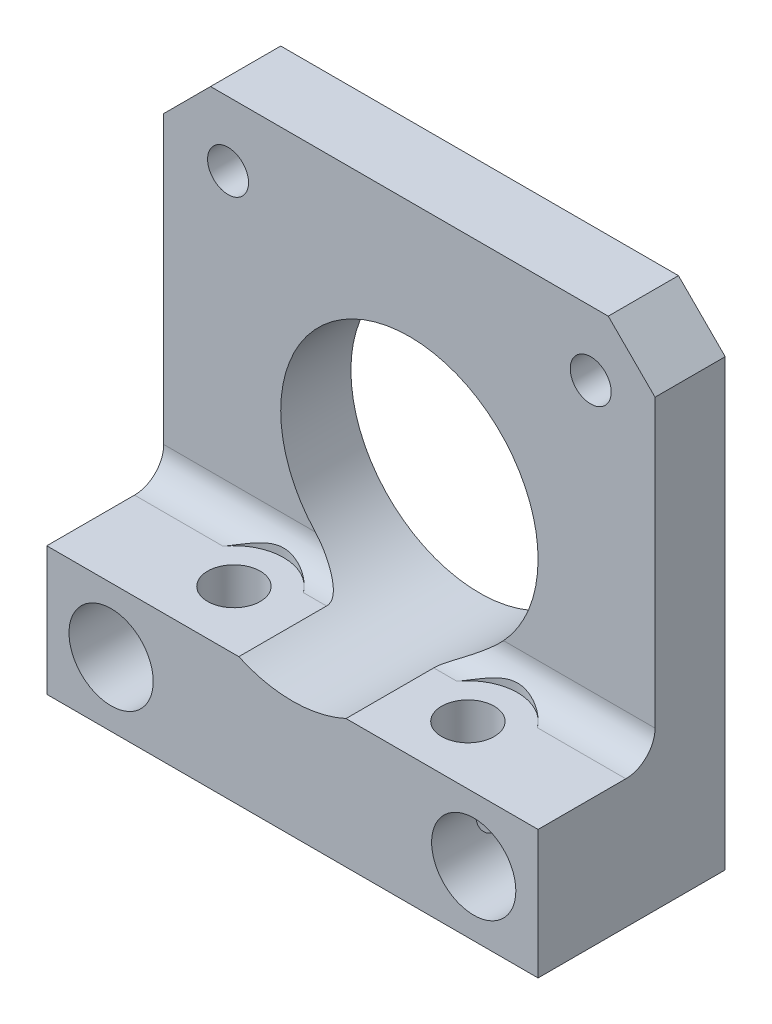
SolidWorks part; units mm, degrees
ref_plane "Plano frontal" through (0, 0, 0) normal (0, 0, 1) x (1, 0, 0)
ref_plane "Plano superior" through (0, 0, 0) normal (0, 1, 0) x (1, 0, 0)
ref_plane "Plano direito" through (0, 0, 0) normal (1, 0, 0) x (0, 0, -1)
sketch "Esboço1" plane through (0, 0, 0) normal (0, 0, 1) x (1, 0, 0)
  line L5 (21, 21) -> (-21, 21)
  line L6 (21, 21) -> (21, -21)
  line L7 (21, -21) -> (-21, -21)
  line L12 (-21, 21) -> (-21, -21)
  line L13 (21, 21) -> (-21, -21) construction
  line L14 (21, -21) -> (-21, 21) construction
  point P0 (0, 0)
  point P1 (0, 0)
  dimension "D1" = 42
  dimension "D2" = 42
extrude "Ressalto-extrusão3" add sketch "Esboço1" along normal blind 6
sketch "Esboço7" plane through (0, 0, 6) normal (0, 0, 1) x (1, 0, 0)
  line L0 (21, -21) -> (21, 21) construction
  line L1 (-21, -21) -> (21, -21)
  line L2 (-21, -21) -> (-21, -10)
  line L3 (-21, -10) -> (21, -10)
  line L4 (21, -21) -> (21, -10)
  dimension "D1" = 11
extrude "Ressalto-extrusão4" add sketch "Esboço7" along normal blind 10
sketch "Esboço6" plane through (0, 0, 0) normal (0, 0, -1) x (-1, 0, 0)
  line L0 (0, 21) -> (0, -21) construction
  line L1 (-21, 21) -> (21, 21) construction
  line L2 (21, -21) -> (-21, -21) construction
  line L4 (-15.5, 15.5) -> (15.5, 15.5) construction
  line L5 (-15.5, 15.5) -> (-15.5, -15.5) construction
  line L6 (-15.5, -15.5) -> (15.5, -15.5) construction
  line L7 (15.5, 15.5) -> (15.5, -15.5) construction
  line L8 (-15.5, 15.5) -> (15.5, -15.5) construction
  line L9 (-15.5, -15.5) -> (15.5, 15.5) construction
  circle A0 centre (0, 0) radius 11
  circle A1 centre (-15.5, 15.5) radius 1.75
  circle A2 centre (15.5, 15.5) radius 1.75
  circle A3 centre (15.5, -15.5) radius 1.75
  circle A4 centre (-15.5, -15.5) radius 1.75
  dimension "D1" = 22
  dimension "D3" = 3.5
  dimension "D2" = 31
extrude "Corte-extrusão3" cut sketch "Esboço6" against normal up to surface (16 mm away) up to face at (0, -15.5, 16)
chamfer "Chanfro1" distance 4 angle 45 2 edges at (-21, 21, 3) (21, 21, 3)
fillet "Filete1" radius 2.5 2 edges at (-12.7913, -10, 6) (12.7913, -10, 6)
sketch "Esboço8" plane through (0, -21, 0) normal (0, -1, 0) x (1, 0, 0)
  line L0 (0, 16) -> (0, 6) construction
  line L1 (-21, 16) -> (21, 16) construction
  line L2 (-13.75, 6) -> (-17.25, 6) construction
  line L3 (-10, 11) -> (10, 11) construction
  circle A0 centre (-10, 11) radius 2.25
  circle A1 centre (10, 11) radius 2.25
  point P11 (0, 11)
  dimension "D2" = 4.5
  dimension "D1" = 20
extrude "Corte-extrusão4" cut sketch "Esboço8" against normal up to surface (11 mm away) up to face at (-12.7913, -10, 12.25)
sketch "Esboço9" plane through (0, 0, 16) normal (0, 0, 1) x (1, 0, 0)
  circle A0 centre (-15.5, -15.5) radius 3.6
  circle A1 centre (15.5, -15.5) radius 3.6
  dimension "D1" = 7.2
extrude "Corte-extrusão5" cut sketch "Esboço9" against normal up to surface (10 mm away) up to face at (-17.25, 15.5, 6)
ref_plane "Plano1" through (0, 0, 0) normal (1, 0, 0) x (0, 0, -1)
sketch "Esboço10" plane through (0, -10, 0) normal (0, 1, 0) x (1, 0, 0)
  circle A0 centre (10, -11) radius 4.25
  circle A1 centre (-10, -11) radius 4.25
  dimension "D1" = 8.5
extrude "Corte-extrusão6" cut sketch "Esboço10" along normal up to surface up to face at (-13.3591, -9.1257, 7.153)
